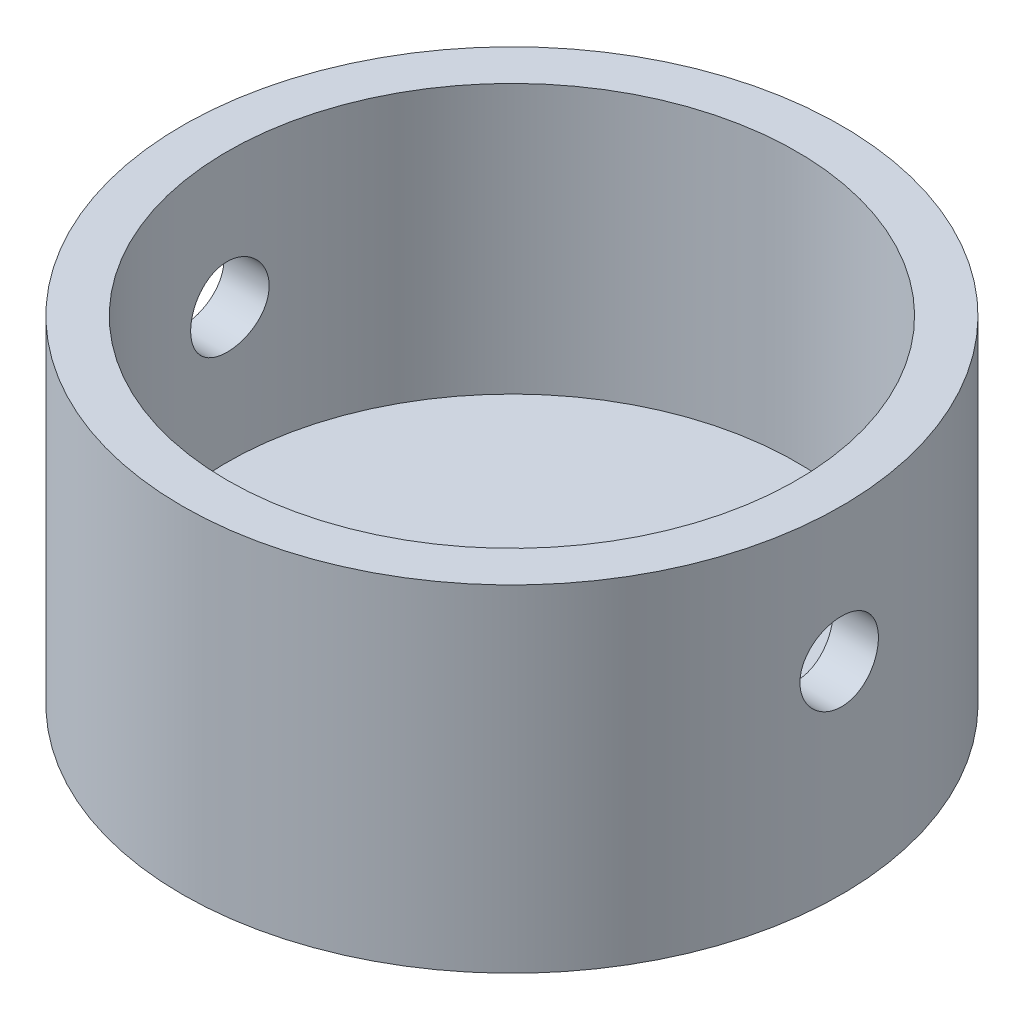
SolidWorks part; units mm, degrees
ref_plane "Front Plane" through (0, 0, 0) normal (0, 0, 1) x (1, 0, 0)
ref_plane "Top Plane" through (0, 0, 0) normal (0, 1, 0) x (1, 0, 0)
ref_plane "Right Plane" through (0, 0, 0) normal (1, 0, 0) x (0, 0, -1)
sketch "Sketch1" plane through (0, 0, 0) normal (0, 1, 0) x (1, 0, 0)
  circle A0 centre (0, 0) radius 12.7 construction
  circle A1 centre (0, 0) radius 14.7
  dimension "D1" = 25.4
  dimension "D2" = 2
extrude "Boss-Extrude1" add sketch "Sketch1" along normal blind 15
sketch "Sketch2" plane through (0, 15, 0) normal (0, 1, 0) x (1, 0, 0)
  circle A0 centre (0, 0) radius 12.7
  dimension "D1" = 25.4
extrude "Cut-Extrude1" cut sketch "Sketch2" against normal offset from surface (12 mm away) 3 up to face at (0, 0, 14.7)
sketch "Sketch3" plane through (0, 0, 0) normal (1, 0, 0) x (0, 0, -1)
  line L0 (0, 15) -> (0, 9) construction
  line L1 (12.7, 15) -> (-12.7, 15) construction
  circle A0 centre (0, 9) radius 1.75
  dimension "D2" = 3.5
  dimension "D1" = 6
extrude "Cut-Extrude2" cut sketch "Sketch3" against normal through all both and the other way through all
sketch "Sketch4" plane through (0, 0, 0) normal (0, -1, 0) x (1, 0, 0)
  circle A0 centre (0, 0) radius 4
  dimension "D1" = 8
extrude "Cut-Extrude3" cut sketch "Sketch4" against normal through all
